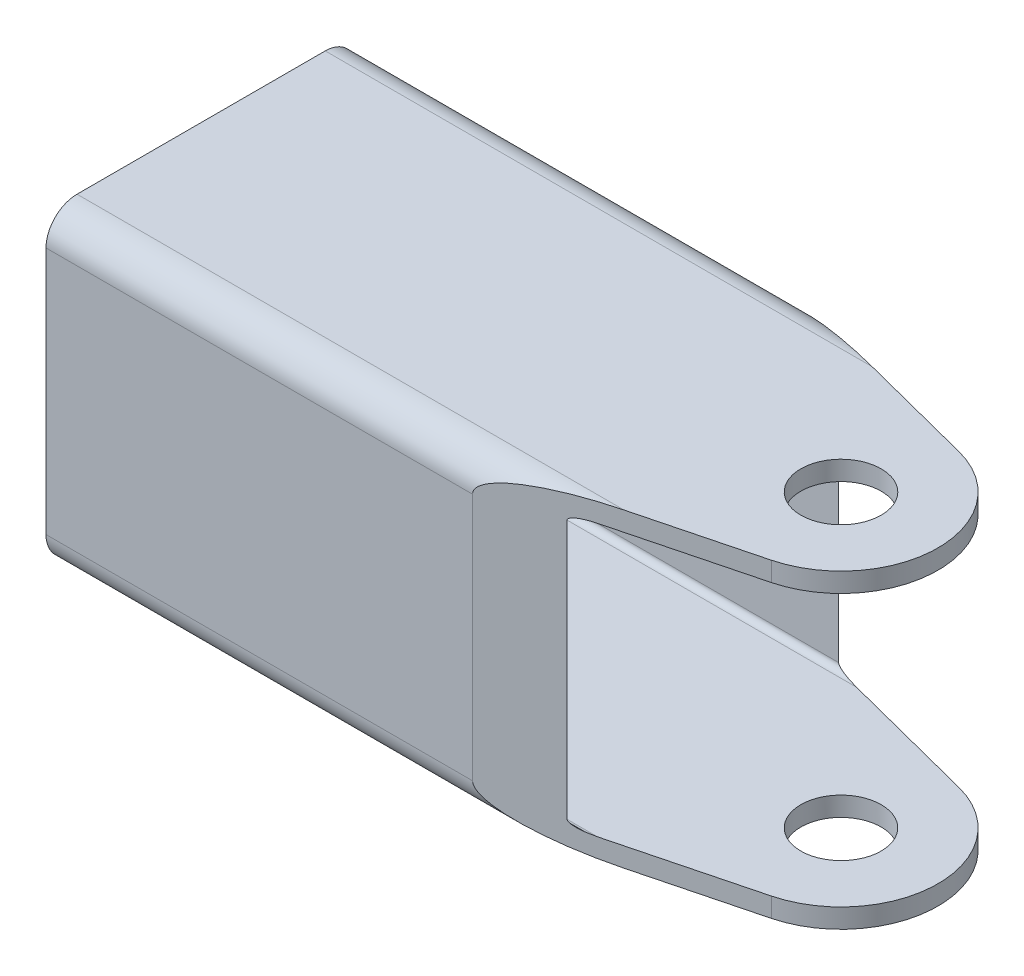
SolidWorks part; units mm, degrees
material "AISI 4130 Steel, annealed at 865C"
ref_plane "Front Plane" through (0, 0, 0) normal (0, 0, 1) x (1, 0, 0)
ref_plane "Top Plane" through (0, 0, 0) normal (0, 1, 0) x (1, 0, 0)
ref_plane "Right Plane" through (0, 0, 0) normal (1, 0, 0) x (0, 0, -1)
sketch "Sketch1" plane through (0, 0, 0) normal (1, 0, 0) x (0, 0, -1)
  line L1 (-10.16, 12.7) -> (10.16, 12.7)
  line L2 (-12.7, 10.16) -> (-12.7, -10.16)
  line L3 (-10.16, -12.7) -> (10.16, -12.7)
  line L4 (12.7, 10.16) -> (12.7, -10.16)
  arc A0 (-10.16, 12.7) -> (-12.7, 10.16) centre (-10.16, 10.16) ccw
  arc A1 (-10.16, -12.7) -> (-12.7, -10.16) centre (-10.16, -10.16) cw
  arc A2 (10.16, 12.7) -> (12.7, 10.16) centre (10.16, 10.16) cw
  arc A3 (12.7, -10.16) -> (10.16, -12.7) centre (10.16, -10.16) cw
  point P4 (0, -12.7)
  point P7 (0, 0)
  point P15 (12.7, 0)
  dimension "D3" = 2.54
  dimension "D4" = 2.54
  dimension "D5" = 2.54
  dimension "D6" = 2.54
  dimension "D1" = 25.4
  dimension "D2" = 20.32
extrude "Boss-Extrude1" add sketch "Sketch1" along normal blind 25.4 and the other way blind 34.925
sketch "Sketch11" plane through (25.4, 0, 0) normal (1, 0, 0) x (0, 0, -1)
  line L0 (-10.16, -12.7) -> (10.16, -12.7) construction
  line L1 (-10.6045, 11.1125) -> (10.6045, 11.1125)
  line L2 (-11.1125, 10.6045) -> (-11.1125, -10.6045)
  line L3 (-10.6045, -11.1125) -> (10.6045, -11.1125)
  line L4 (11.1125, 10.6045) -> (11.1125, -10.6045)
  line L5 (10.16, 12.7) -> (-10.16, 12.7) construction
  line L6 (12.7, -10.16) -> (12.7, 10.16) construction
  line L7 (-12.7, 10.16) -> (-12.7, -10.16) construction
  arc A0 (10.6045, 11.1125) -> (11.1125, 10.6045) centre (10.6045, 10.6045) cw
  arc A1 (10.6045, -11.1125) -> (11.1125, -10.6045) centre (10.6045, -10.6045) ccw
  arc A2 (-11.1125, -10.6045) -> (-10.6045, -11.1125) centre (-10.6045, -10.6045) ccw
  arc A3 (-10.6045, 11.1125) -> (-11.1125, 10.6045) centre (-10.6045, 10.6045) ccw
  dimension "D1" = 1.5875
  dimension "D2" = 1.5875
  dimension "D3" = 1.5875
  dimension "D4" = 1.5875
  dimension "D5" = 0.508
extrude "Cut-Extrude4" cut sketch "Sketch11" against normal through all
sketch "Sketch12" plane through (0, 12.7, 0) normal (0, 1, 0) x (1, 0, 0)
  line L1 (0, 12.7) -> (50.8, 12.7)
  line L2 (50.8, 12.7) -> (50.8, -12.7)
  line L12 (50.8, -12.7) -> (0, -12.7)
  line L13 (19.4444, -7.6861) -> (0, -12.7)
  line L14 (19.4444, 7.6861) -> (0, 12.7)
  line L15 (-34.925, -12.7) -> (25.4, -12.7) construction
  line L16 (-34.925, 12.7) -> (25.4, 12.7) construction
  line L18 (25.4, 10.16) -> (25.4, -10.16) construction
  arc A1 (19.4444, -7.6861) -> (19.4444, 7.6861) centre (17.4625, 0) ccw
  point P8 (18.1688, 9.2165)
  dimension "D2" = 50.8
  dimension "D1" = 17.4625
extrude "Cut-Extrude5" cut sketch "Sketch12" against normal through all region at (34.888, 12.7, 0) region at (20.955, 12.7, -8.1283) region at (20.955, 12.7, 8.1283)
sketch "Sketch14" plane through (0, 12.7, 0) normal (0, 1, 0) x (1, 0, 0)
  circle A0 centre (17.4625, 0) radius 3.2893
  arc A2 (19.4444, -7.6861) -> (19.4444, 7.6861) centre (17.4625, 0) ccw construction
  point P0 (17.4625, 0)
  point P6 (25.4, 0)
  dimension "D2" = 6.5786
  dimension "D1" = 7.9375
  dimension "D3" = 17.4625
extrude "Cut-Extrude6" cut sketch "Sketch14" against normal through all
